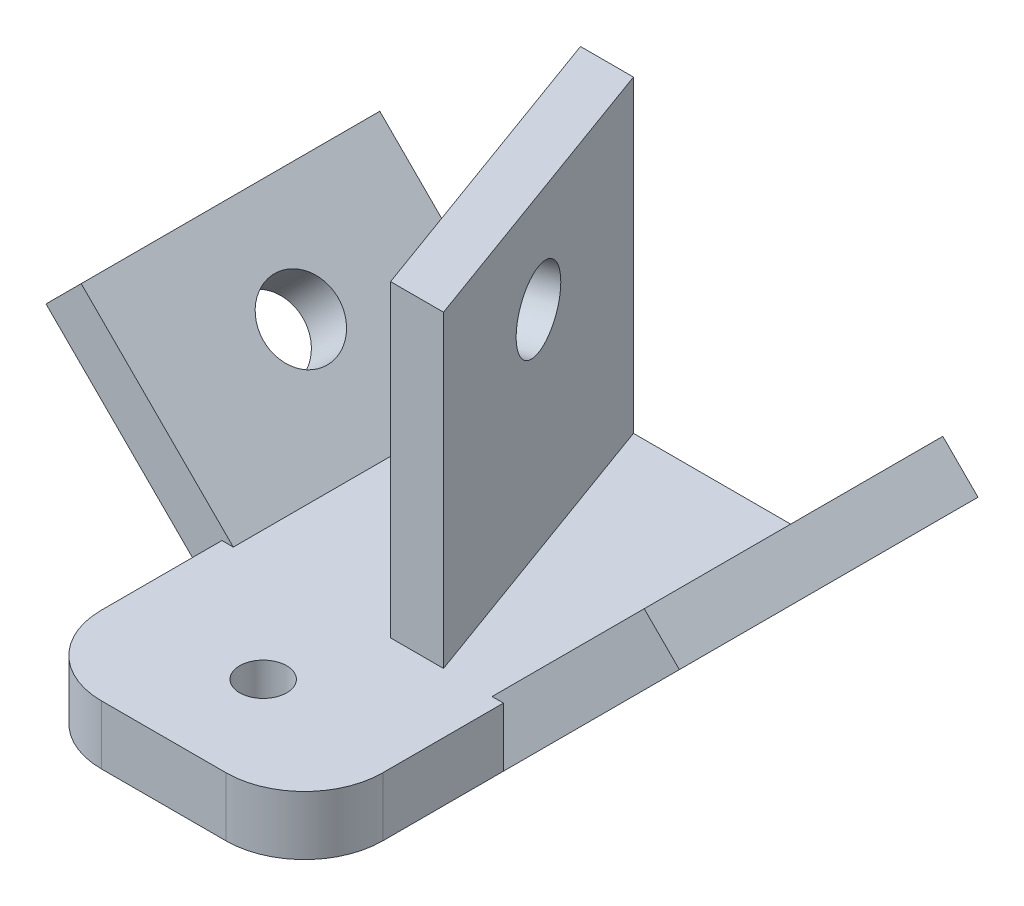
SolidWorks part; units mm, degrees
ref_plane "Front Plane" through (0, 0, 0) normal (0, 0, 1) x (1, 0, 0)
ref_plane "Top Plane" through (0, 0, 0) normal (0, 1, 0) x (1, 0, 0)
ref_plane "Right Plane" through (0, 0, 0) normal (1, 0, 0) x (0, 0, -1)
sketch "Sketch1" plane through (0, 0, 0) normal (0, 0, 1) x (1, 0, 0)
  line L0 (-35.921, 35.921) -> (0, 0)
  line L1 (0, 0) -> (35.921, 35.921)
  line L2 (35.921, 35.921) -> (40.4112, 31.4309)
  line L3 (40.4112, 31.4309) -> (0, -8.9803)
  line L4 (0, -8.9803) -> (-40.4112, 31.4309)
  line L5 (-40.4112, 31.4309) -> (-35.921, 35.921)
  line L6 (0, -8.9803) -> (0, 0) construction
  point P2 (7.0733, 5.6375)
  point P8 (0, 0)
  dimension "D1" = 6.35
  dimension "D2" = 50.8
extrude "Boss-Extrude1" add sketch "Sketch1" along normal mid plane 38.1
sketch "Sketch2" plane through (0, 0, 0) normal (0, 1, 0) x (1, 0, 0)
  line L0 (-10.3124, 19.05) -> (-3.5549, 19.05)
  line L1 (0, 19.05) -> (-35.921, 19.05) construction
  line L2 (-3.5549, 19.05) -> (10.3124, -19.05)
  line L3 (35.921, -19.05) -> (0, -19.05) construction
  line L4 (10.3124, -19.05) -> (3.5549, -19.05)
  line L5 (3.5549, -19.05) -> (-10.3124, 19.05)
  line L6 (-6.9336, 19.05) -> (6.9336, -19.05) construction
  line L7 (0, -19.05) -> (-35.921, -19.05) construction
  point P10 (0, 0)
  point P11 (-3.4868, 19.05)
  dimension "D1" = 6.35
  dimension "D2" = 70
extrude "Boss-Extrude2" add sketch "Sketch2" against normal up to body and the other way blind 50.8 from offset 5.08 separate body
sketch "Sketch3" plane through (-4.4901, -4.4901, 0) normal (-0.7071, -0.7071, 0) x (0, 0, 1)
  line L0 (19.05, 50.8) -> (-19.05, 50.8) construction
  circle A0 centre (0, 38.1) radius 4.7625
  point P4 (0, 50.8)
  dimension "D1" = 9.525
  dimension "D2" = 12.7
extrude "Cut-Extrude1" cut sketch "Sketch3" against normal up to next
mirror "Mirror1" about plane through (0, 0, 0) normal (1, 0, 0) of "Cut-Extrude1"
sketch "Sketch4" plane through (2.9835, 0, -1.0859) normal (0.9397, 0, -0.342) x (-0.342, 0, -0.9397)
  line L0 (-21.4282, 55.88) -> (19.117, 55.88) construction
  circle A0 centre (-1.1556, 43.18) radius 4.7625
  point P4 (-1.1556, 55.88)
  dimension "D2" = 9.525
  dimension "D1" = 12.7
extrude "Cut-Extrude2" cut sketch "Sketch4" against normal up to next
sketch "Sketch5" plane through (0, 0, 19.05) normal (0, 0, 1) x (1, 0, 0)
  line L0 (-16.51, 16.51) -> (16.51, 16.51)
  line L1 (0, 0) -> (-35.921, 35.921) construction
  line L2 (35.921, 35.921) -> (10.3124, 10.3124) construction
  line L3 (16.51, 16.51) -> (0, 0)
  line L4 (0, 0) -> (-16.51, 16.51)
  dimension "D1" = 16.51
extrude "Boss-Extrude3" add sketch "Sketch5" against normal up to surface (38.1 mm away) up to face at (-2.7735, 25.1351, -19.05)
chamfer "Chamfer1" distance 25.4 angle 45 1 edges at (0, -8.9803, 0)
sketch "Sketch6" plane through (0, 8.9803, 0) normal (0, -1, 0) x (1, 0, 0)
  line L1 (-17.9605, 19.05) -> (17.9605, 19.05)
  line L2 (-17.9605, 19.05) -> (-17.9605, 44.45)
  line L3 (-17.9605, 44.45) -> (17.9605, 44.45)
  line L4 (17.9605, 19.05) -> (17.9605, 44.45)
  line L5 (-17.9605, 19.05) -> (17.9605, 44.45) construction
  line L6 (-17.9605, 44.45) -> (17.9605, 19.05) construction
  point P4 (0, 31.75)
  point P6 (0, 0)
  point P9 (0, 0)
  dimension "D1" = 25.4
extrude "Boss-Extrude4" add sketch "Sketch6" against normal up to surface (7.5297 mm away) up to face at (-9.9444, 16.51, 0)
sketch "Sketch7" plane through (0, 16.51, 0) normal (0, 1, 0) x (1, 0, 0)
  line L0 (-17.9605, -44.45) -> (-17.9605, -19.05) construction
  line L1 (17.9605, -44.45) -> (-17.9605, -44.45) construction
  circle A0 centre (0, -31.75) radius 3
  point P4 (-17.9605, -31.75)
  point P7 (0, -44.45)
  dimension "D1" = 6
extrude "Cut-Extrude3" cut sketch "Sketch7" against normal through all
fillet "Fillet1" radius 10 2 edges at (17.9605, 12.7451, 44.45) (-17.9605, 12.7451, 44.45)
